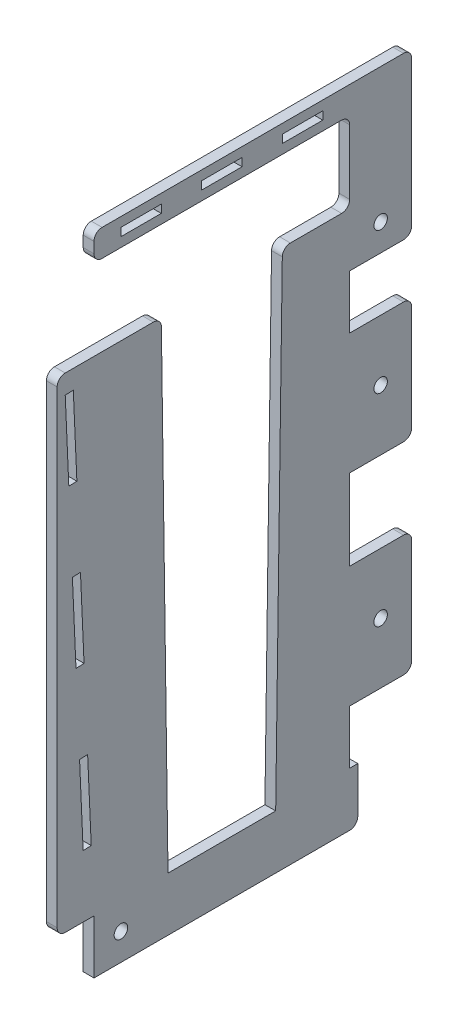
SolidWorks part; units mm, degrees
ref_plane "Front" through (0, 0, 0) normal (0, 0, 1) x (1, 0, 0)
ref_plane "Top" through (0, 0, 0) normal (0, 1, 0) x (1, 0, 0)
ref_plane "Right" through (0, 0, 0) normal (1, 0, 0) x (0, 0, -1)
sketch "Sketch1" plane through (0, 0, 0) normal (1, 0, 0) x (0, 0, -1)
  line L0 (0, 0) -> (-95, 0)
  line L1 (-95, 0) -> (-95, 200)
  line L2 (-95, 200) -> (23, 200)
  line L3 (23, 200) -> (23, 180)
  line L4 (23, 180) -> (0, 180)
  line L5 (0, 180) -> (0, 160)
  line L6 (0, 160) -> (23, 160)
  line L7 (23, 160) -> (23, 115)
  line L8 (23, 115) -> (0, 115)
  line L9 (0, 115) -> (0, 85)
  line L10 (0, 85) -> (23, 85)
  line L11 (23, 85) -> (23, 40)
  line L12 (23, 40) -> (0, 40)
  line L13 (0, 40) -> (0, 0)
  circle A0 centre (11.5, 190) radius 2.5
  circle A1 centre (11.5, 137.5) radius 2.5
  circle A2 centre (11.5, 62.5) radius 2.5
  point P4 (-95, 100)
  point P18 (0, 100)
  point P37 (11.5, 180)
  point P38 (23, 190)
  point P39 (23, 137.5)
  point P40 (23, 62.5)
  dimension "D6" = 5
  dimension "D10" = 5
  dimension "D11" = 5
  dimension "D1" = 95
  dimension "D2" = 20
  dimension "D3" = 20
  dimension "D4" = 200
  dimension "D5" = 30
  dimension "D7" = 40
  dimension "D9" = 23
extrude "Boss-Extrude1" add sketch "Sketch1" along normal blind 4
sketch "Sketch12" plane through (4, 0, 0) normal (1, 0, 0) x (0, 0, -1)
  line L0 (-95, 200) -> (-95, 0) construction
  line L1 (-95, 0) -> (0, 0) construction
  circle A0 centre (-85, 10) radius 2.5
  dimension "D1" = 5
  dimension "D2" = 10
  dimension "D3" = 10
sketch "Sketch4" plane through (4, 0, 0) normal (1, 0, 0) x (0, 0, -1)
  line L0 (0, 230) -> (0, 200)
  line L1 (0, 240) -> (-95, 240)
  line L2 (-95, 240) -> (-95, 230)
  line L3 (-95, 230) -> (0, 230)
  line L4 (23, 200) -> (-95, 200) construction
  line L5 (0, 160) -> (0, 180) construction
  line L7 (-85, 236.5) -> (-70, 236.5)
  line L8 (-85, 236.5) -> (-85, 233.5)
  line L9 (-85, 233.5) -> (-70, 233.5)
  line L10 (-70, 236.5) -> (-70, 233.5)
  line L11 (-55, 236.5) -> (-40, 236.5)
  line L12 (-55, 236.5) -> (-55, 233.5)
  line L13 (-55, 233.5) -> (-40, 233.5)
  line L14 (-40, 236.5) -> (-40, 233.5)
  line L15 (-25, 236.5) -> (-10, 236.5)
  line L16 (-25, 236.5) -> (-25, 233.5)
  line L17 (-25, 233.5) -> (-10, 233.5)
  line L18 (-10, 236.5) -> (-10, 233.5)
  line L19 (-95, 235) -> (0, 235) construction
  line L20 (-55, 235) -> (-40, 235) construction
  line L22 (0, 240) -> (23, 240)
  line L23 (23, 240) -> (23, 200)
  point P0 (0, 0)
  point P29 (-47.5, 235)
  point P30 (-47.5, 235)
  line M19 (23, 200) -> (-95, 200)
  dimension "D1" = 15
  dimension "D2" = 15
  dimension "D3" = 15
  dimension "D4" = 3
  dimension "D5" = 10
  dimension "D7" = 10
  dimension "D8" = 95
  dimension "D6" = 30
  dimension "D9" = 10
extrude "Boss-Extrude2" add sketch "Sketch4" against normal blind 4 contours L3 L1 L2 L7 L10 L9 L8 L11 L14 L13 L12 L15 L18 L17 L16 M19 region at (4, 231.246, 47.5)
sketch "Sketch5" plane through (4, 0, 0) normal (1, 0, 0) x (0, 0, -1)
  line L0 (-103, 200) -> (-95, 20) construction
  line L1 (-95, 0) -> (0, 0) construction
  line L2 (-102.6882, 192.9853) -> (-105.6853, 192.8521)
  line L3 (-102.6882, 192.9853) -> (-101.3562, 163.0149)
  line L4 (-101.3562, 163.0149) -> (-104.3533, 162.8817)
  line L5 (-105.6853, 192.8521) -> (-104.3533, 162.8817)
  line L6 (-100.0242, 133.0444) -> (-103.0212, 132.9112)
  line L7 (-100.0242, 133.0444) -> (-98.6922, 103.074)
  line L8 (-98.6922, 103.074) -> (-101.6892, 102.9408)
  line L9 (-103.0212, 132.9112) -> (-101.6892, 102.9408)
  line L10 (-97.3602, 73.1036) -> (-100.3572, 72.9704)
  line L11 (-97.3602, 73.1036) -> (-96.0281, 43.1332)
  line L12 (-96.0281, 43.1332) -> (-99.0252, 43)
  line L13 (-100.3572, 72.9704) -> (-99.0252, 43)
  line L16 (0, 200) -> (-95, 200) construction
  line L20 (-95, 200) -> (-108.6853, 200)
  line L21 (-95, 200) -> (-95, 20)
  line L22 (-95, 20) -> (-108.6853, 20)
  line L23 (-108.6853, 200) -> (-108.6853, 20)
  line M27 (-95, 200) -> (-95, 0)
  dimension "D6" = 30
  dimension "D1" = 3
  dimension "D2" = 30
  dimension "D3" = 30
  dimension "D4" = 30
  dimension "D5" = 8
  dimension "D8" = 30
  dimension "D9" = 3
  dimension "D7" = 23
  dimension "D10" = 20
extrude "Boss-Extrude3" add sketch "Sketch5" against normal blind 4 contours L0 L20 L23 L22 L12 L13 L10 L8 L9 L6 L4 L5 L2 | L20 L0 L3 L7 L11 M27 region at (4, 140, 97.6667) region at (4, 93.8748, 104.064)
sketch "Sketch6" plane through (4, 0, 0) normal (1, 0, 0) x (0, 0, -1)
  line L0 (-70, 200) -> (-67.5, 20)
  line L1 (0, 200) -> (-108.6853, 200) construction
  line L2 (-67.5, 20) -> (-27.5, 20)
  line L3 (-27.5, 20) -> (-25, 200)
  line L4 (-95, 0) -> (0, 0) construction
  line L5 (0, 20) -> (-95, 20) construction
  line L6 (0, 200) -> (-95, 200) construction
  line L9 (0, 160) -> (0, 180) construction
  line L11 (-25, 200) -> (-70, 200) construction
  line L14 (0, 0) -> (0, 40) construction
  point P16 (-47.5, 20)
  point P19 (-47.5, 20)
  point P22 (-47.5, 200)
  point P23 (-47.5, 200)
  line M29 (0, 200) -> (-108.6853, 200)
  dimension "D1" = 20
  dimension "D2" = 40
  dimension "D3" = 45
  dimension "D4" = 95
extrude "Cut-Extrude3" cut sketch "Sketch6" against normal blind 4 contours L2 L3 L0 M29 region at (4, 111.7647, 47.5)
sketch "Sketch11" plane through (0, 0, 0) normal (-1, 0, 0) x (0, 0, 1)
  line L0 (67.5, 20) -> (27.5, 20) construction
  line L1 (0, 0) -> (-3, 0)
  line L2 (0, 0) -> (0, 20)
  line L3 (0, 20) -> (-3, 20)
  line L4 (-3, 0) -> (-3, 20)
  line L5 (95, 0) -> (0, 0) construction
  line L6 (0, 0) -> (0, 40) construction
  dimension "D1" = 3
extrude "Boss-Extrude5" add sketch "Sketch11" against normal blind 4
fillet "Fillet1" radius 3 15 edges at (2, 200, 70) (2, 200, 25) (2, 20, 108.6853) (2, 40, -23) (2, 85, -23) (2, 115, -23) (2, 160, -23) (2, 180, -23) (2, 240, -23) (2, 230, 0) (2, 230, 95) (2, 240, 95) (2, 200, 108.6853) (2, 0, -3)
extrude "Cut-Extrude7" cut sketch "Sketch12" against normal blind 4
equation "\"D2@Sketch4\"=\"D1@Sketch4\""
equation "\"D3@Sketch4\"=\"D1@Sketch4\""
equation "\"D4@Sketch5\"=\"D3@Sketch5\""
equation "\"D2@Sketch5\"=\"D3@Sketch5\""
equation "\"D6@Sketch5\"=\"D8@Sketch5\""
